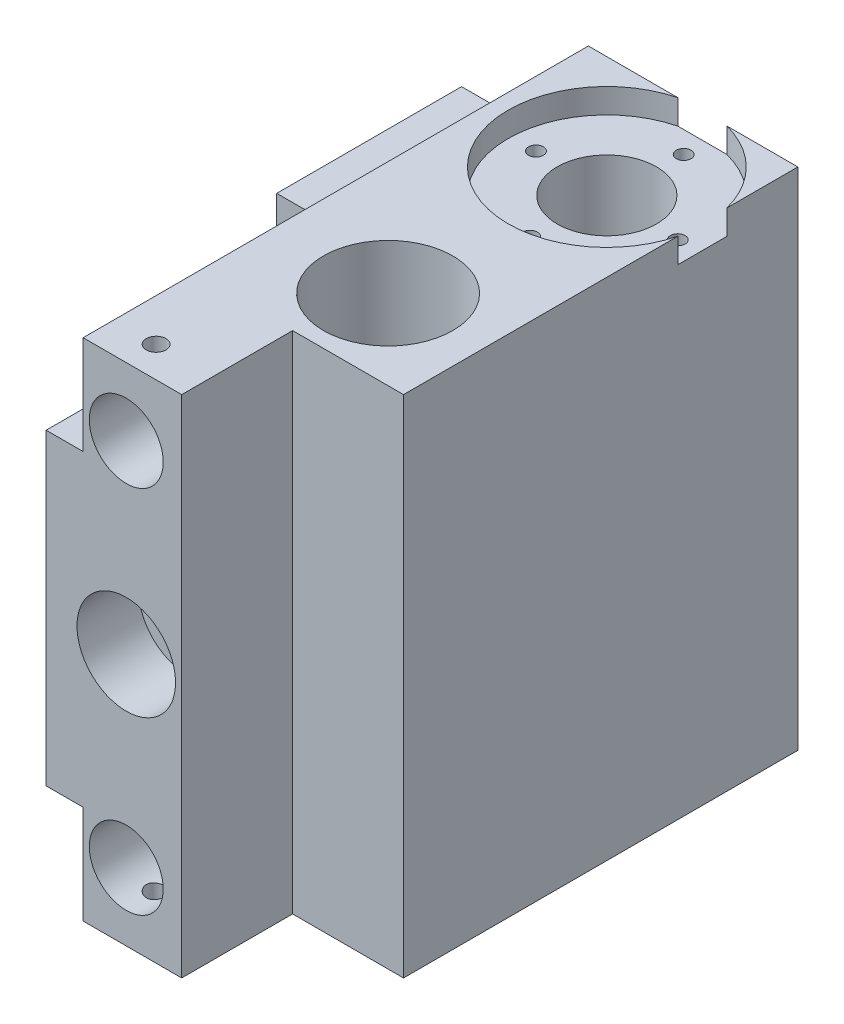
SolidWorks part; units mm, degrees
material "1060 Alloy"
ref_plane "Front Plane" through (0, 0, 0) normal (0, 0, 1) x (1, 0, 0)
ref_plane "Top Plane" through (0, 0, 0) normal (0, 1, 0) x (1, 0, 0)
ref_plane "Right Plane" through (0, 0, 0) normal (1, 0, 0) x (0, 0, -1)
sketch "Sketch1" plane through (0, 0, 0) normal (0, 0, 1) x (1, 0, 0)
  line L0 (-27, -6.0963) -> (-27, -75.9037) construction
  line L1 (0, 0) -> (-40, 0)
  line L2 (0, 0) -> (0, -82)
  line L3 (0, -82) -> (-40, -82)
  line L4 (-40, 0) -> (-40, -82)
  circle A0 centre (-27, -41) radius 5.5
  circle A1 centre (-27, -11) radius 6
  circle A2 centre (-27, -71) radius 6
  dimension "D3" = 11
  dimension "D4" = 12
  dimension "D5" = 12
  dimension "D1" = 40
  dimension "D2" = 82
  dimension "D6" = 11
  dimension "D7" = 30
  dimension "D8" = 13
  dimension "D9" = 30
  dimension "D10" = 11
extrude "Boss-Extrude1" add sketch "Sketch1" along normal blind 12
sketch "Sketch2" plane through (0, 0, 0) normal (0, 0, -1) x (-1, 0, 0)
  line L0 (0, -82) -> (0, 0) construction
  line L1 (40, -82) -> (0, -82) construction
  line L2 (40, 0) -> (40, -82) construction
  line L3 (0, 0) -> (40, 0) construction
  line L4 (0, -82) -> (0, 0)
  line L5 (40, -82) -> (0, -82)
  line L6 (40, 0) -> (40, -82)
  line L7 (0, 0) -> (40, 0)
  circle A0 centre (27, -41) radius 5.5 construction
  circle A1 centre (27, -41) radius 5.5
extrude "Boss-Extrude2" add sketch "Sketch2" along normal blind 70
sketch "Sketch3" plane through (0, 0, 0) normal (0, 1, 0) x (1, 0, 0)
  line L0 (-40, -5) -> (0, -5) construction
  line L1 (-40, -12) -> (-40, 70) construction
  line L2 (0, -12) -> (0, 70) construction
  line L3 (0, -12) -> (-40, -12) construction
  circle A0 centre (-27.1548, -7) radius 1.6
  dimension "D1" = 3.2
  dimension "D2" = 5
  dimension "D3" = 13
extrude "Cut-Extrude1" cut sketch "Sketch3" against normal blind 10
sketch "Sketch4" plane through (0, -82, 0) normal (0, -1, 0) x (1, 0, 0)
  circle A1 centre (-27.1548, 7) radius 1.6
  circle A2 centre (-27.1548, 7) radius 1.6
  dimension "D1" = 0
extrude "Cut-Extrude2" cut sketch "Sketch4" against normal blind 10
sketch "Sketch5" plane through (0, 0, 0) normal (0, 1, 0) x (1, 0, 0)
  line L0 (-15.5, 70) -> (-15.5, 49) construction
  line L1 (-40, 70) -> (0, 70) construction
  line L2 (0, -12) -> (-40, -12) construction
  line L3 (0, -12) -> (0, 70) construction
  line L4 (-15.5, 60) -> (-15.5, 49) construction
  line L5 (-15.5, 29.5) -> (-15.5, -12) construction
  line L6 (-15.5, 29.5) -> (-15.5, 8.5) construction
  circle A1 centre (-15.5, 19) radius 10.5
  circle A2 centre (-15.5, 54.5) radius 5.5
  dimension "D2" = 11
  dimension "D3" = 25
  dimension "D4" = 21
  dimension "D1" = 15.5
  dimension "D6" = 51
extrude "Cut-Extrude3" cut sketch "Sketch5" against normal blind 100
sketch "Sketch6" plane through (0, 0, 0) normal (0, 1, 0) x (1, 0, 0)
  circle A0 centre (-15.5, 54.5) radius 16
  dimension "D1" = 32
extrude "Cut-Extrude4" cut sketch "Sketch6" against normal blind 4
sketch "Sketch19" plane through (0, -4, 0) normal (0, 1, 0) x (1, 0, 0)
  circle A0 centre (-15.5, 54.5) radius 8.05
  dimension "D1" = 16.1
extrude "Cut-Extrude17" cut sketch "Sketch19" against normal blind 16
sketch "Sketch12" plane through (0, -4, 0) normal (0, 1, 0) x (1, 0, 0)
  line L1 (-3.5097, 54.0181) -> (-3.0278, 66.0084) construction
  line L2 (-3.0278, 66.0084) -> (-15.0181, 66.4903) construction
  line L3 (-27.4903, 54.9819) -> (-27.9722, 42.9916) construction
  line L4 (-27.9722, 42.9916) -> (-15.9819, 42.5097) construction
  circle A0 centre (-15.5, 54.5) radius 12 construction
  circle A1 centre (-15.9819, 42.5097) radius 1.2
  circle A2 centre (-3.5097, 54.0181) radius 1.2
  circle A3 centre (-15.0181, 66.4903) radius 1.2
  circle A4 centre (-27.4903, 54.9819) radius 1.2
  dimension "D1" = 24
  dimension "D2" = 2.4
extrude "Cut-Extrude12" cut sketch "Sketch12" against normal blind 12
sketch "Sketch13" plane through (0, 0, -70) normal (0, 0, -1) x (-1, 0, 0)
  line L1 (40, 0) -> (60, 0)
  line L2 (40, 0) -> (40, -70)
  line L3 (40, -70) -> (60, -70)
  line L4 (60, 0) -> (60, -70)
  dimension "D1" = 20
  dimension "D2" = 70
extrude "Boss-Extrude3" add sketch "Sketch13" against normal blind 30
sketch "Sketch15" plane through (0, 0, -70) normal (0, 0, -1) x (-1, 0, 0)
  line L0 (34, 0) -> (34, -16)
  line L1 (60, 0) -> (19.4686, 0) construction
  line L2 (34, -16) -> (54.5811, -16)
  line L4 (34, -82) -> (34, -66)
  line L5 (0, -82) -> (40, -82) construction
  line L6 (34, -66) -> (54.5811, -66)
  line L7 (54.5811, -66) -> (54.5811, -16)
  line L8 (34, 0) -> (77.5206, 0)
  line L9 (77.5206, 0) -> (77.5206, -82)
  line L10 (77.5206, -82) -> (34, -82)
  line L11 (60, -70) -> (60, 0) construction
  dimension "D1" = 26
  dimension "D2" = 50
  dimension "D3" = 16
extrude "Cut-Extrude14" cut sketch "Sketch15" against normal blind 115
sketch "Sketch20" plane through (0, -82, 0) normal (0, -1, 0) x (1, 0, 0)
  line L1 (0, 12) -> (-18, 12)
  line L2 (0, 12) -> (0, -6)
  line L3 (0, -6) -> (-18, -6)
  line L4 (-18, 12) -> (-18, -6)
  dimension "D1" = 18
  dimension "D2" = 18
extrude "Cut-Extrude18" cut sketch "Sketch20" against normal blind 100
sketch "Sketch21" plane through (0, 0, 12) normal (0, 0, 1) x (1, 0, 0)
  circle A0 centre (-27, -41) radius 8
  dimension "D1" = 16
extrude "Cut-Extrude19" cut sketch "Sketch21" against normal blind 10
